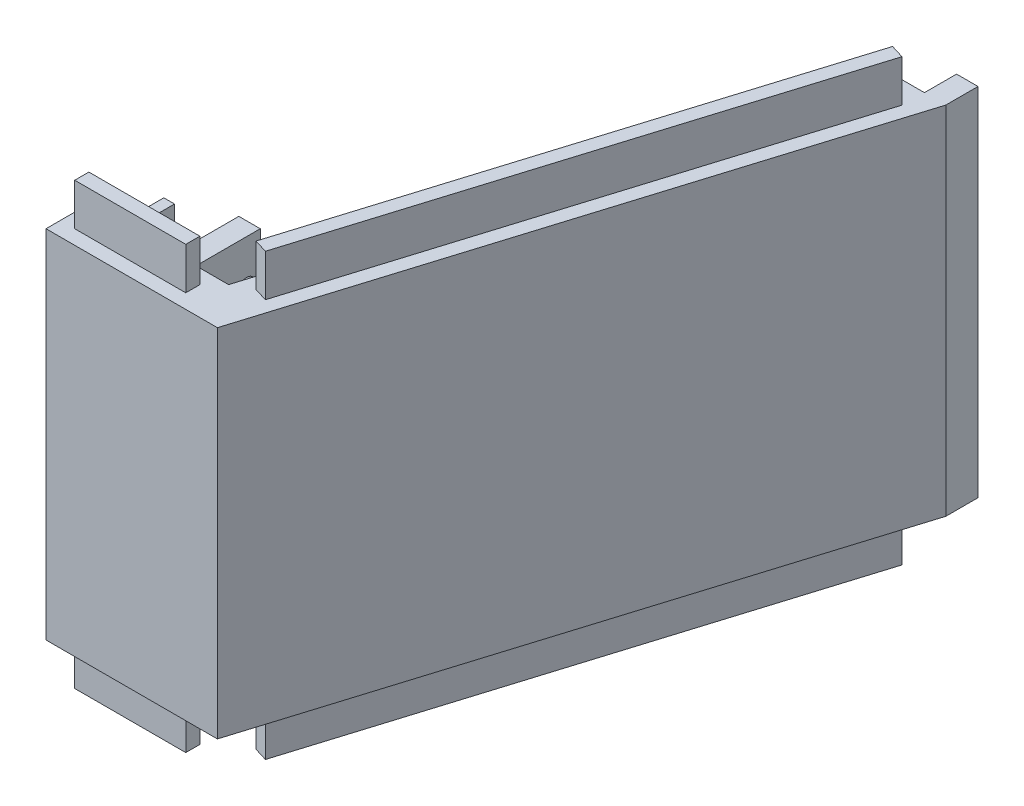
SolidWorks part; units mm, degrees
ref_plane "Front Plane" through (0, 0, 0) normal (1, 0, 0) x (0, 1, 0)
ref_plane "Top Plane" through (0, 0, 0) normal (0, 0, 1) x (0, 1, 0)
ref_plane "Right Plane" through (0, 0, 0) normal (0, 1, 0) x (-1, 0, 0)
sketch "Sketch1" plane through (0, 0, 0) normal (0, 1, 0) x (-1, 0, 0)
  line L0 (-10.3119, 17.5706) -> (29.6881, 147.5706)
  line L1 (-10.3119, 10.0706) -> (-5.3119, 10.0706)
  line L2 (-10.3119, 10.0706) -> (-10.3119, 17.5706)
  line L3 (-10.3119, 17.5706) -> (-5.3119, 17.5706)
  line L4 (-5.3119, 10.0706) -> (-5.3119, 17.5706)
  line L13 (-10.3119, 17.5706) -> (29.6881, 147.5706)
  line L14 (-10.3119, 17.5706) -> (-0.7541, 14.6298)
  line L15 (-10.3119, 17.5706) -> (69.6881, 17.5706) construction
  line L16 (-10.3119, 17.5706) -> (-10.3119, 137.5706) construction
  line L17 (-10.3119, 137.5706) -> (69.6881, 137.5706) construction
  line L18 (69.6881, 17.5706) -> (69.6881, 137.5706) construction
  line L19 (69.6881, 137.5706) -> (29.6881, 137.5706)
  line L20 (69.6881, 137.5706) -> (69.6881, 147.5706)
  line L21 (69.6881, 147.5706) -> (29.6881, 147.5706)
  line L22 (29.6881, 137.5706) -> (29.6881, 147.5706)
  line L23 (29.6881, 147.5706) -> (39.2459, 144.6298)
  line L24 (-0.7541, 14.6298) -> (39.2459, 144.6298)
  line L25 (-5.3119, 17.5706) -> (0.1508, 17.5706)
  dimension "D1" = 7.5
  dimension "D2" = 5
  dimension "D3" = 120
  dimension "D4" = 80
  dimension "D6" = 40
  dimension "D7" = 10
extrude "Boss-Extrude1" add sketch "Sketch1" along normal blind 83.125 contours L24 L19 L20 L21 L23 | L19 L24 L23 L22 | L3 L25 L24 L19 L22 L0 | L14 L2 L1 L4 | L3 L14 L4 region at (7.9071, 0, 13.4507) region at (-13.566, 0, 78.3373) region at (6.9786, 0, 17.0578) region at (-33.743, 0, 142.0805) region at (-53.299, 0, 142.6816)
sketch "Sketch2" plane through (0, 83.125, 0) normal (0, 1, 0) x (-1, 0, 0)
  line L0 (37.0738, 137.5706) -> (0.1508, 17.5706)
  line L1 (37.0738, 137.5706) -> (69.6881, 137.5706)
  line L2 (37.0738, 137.5706) -> (37.0738, 147.5706)
  line L3 (37.0738, 147.5706) -> (69.6881, 147.5706)
  line L4 (69.6881, 137.5706) -> (69.6881, 147.5706)
  line L5 (37.0738, 137.5706) -> (27.5161, 140.5115)
  line L6 (0.1508, 17.5706) -> (-9.407, 20.5115)
  line L7 (27.5161, 140.5115) -> (-9.407, 20.5115)
  line L9 (32.8868, 135.3539) -> (-2.0659, 21.7577)
  line L10 (-2.0659, 21.7577) -> (-5.22, 22.7281)
  line L11 (29.7327, 136.3244) -> (-5.22, 22.7281)
  line L12 (32.8868, 135.3539) -> (29.7327, 136.3244)
  line L13 (40.4238, 140.9206) -> (40.4238, 144.2206)
  line L14 (40.4238, 144.2206) -> (66.3381, 144.2206)
  line L15 (66.3381, 140.9206) -> (66.3381, 144.2206)
  line L16 (40.4238, 140.9206) -> (66.3381, 140.9206)
  line L17 (69.6881, 137.5706) -> (69.6881, 147.5706) construction
  line L18 (29.7327, 136.3244) -> (33.1931, 147.5706)
  line L20 (32.8868, 135.3539) -> (36.6458, 147.5706)
  line L21 (36.6458, 147.5706) -> (33.1931, 147.5706)
  line L22 (40.4238, 144.2206) -> (32.1623, 144.2206)
  line L23 (32.1623, 144.2206) -> (31.1469, 140.9206)
  line L24 (31.1469, 140.9206) -> (40.4238, 140.9206)
  line L25 (-10.3119, 17.5706) -> (29.6881, 147.5706) construction
  dimension "D1" = 3.35
extrude "Boss-Extrude2" add sketch "Sketch2" along normal blind 9.8 contours L9 L12 L11 L10 | L13 L16 L15 L14 region at (-53.381, 83.125, 142.5706) region at (-13.8334, 83.125, 79.041)
ref_plane "Plane1" through (0, 41.5625, 0) normal (0, 1, 0) x (1, 0, 0)
mirror "Mirror1" about plane through (0, 41.5625, 0) normal (0, 1, 0) of "Boss-Extrude2"
sketch "Sketch3" plane through (0, 83.125, 0) normal (0, 1, 0) x (-1, 0, 0)
  line L1 (6.3046, 37.5706) -> (69.6881, 37.5706) construction
  line L2 (6.3046, 37.5706) -> (6.3046, 137.5706) construction
  line L3 (6.3046, 137.5706) -> (69.6881, 137.5706) construction
  line L4 (69.6881, 37.5706) -> (69.6881, 137.5706) construction
  line L5 (69.6881, 37.5706) -> (6.3046, 37.5706)
  line L6 (69.6881, 37.5706) -> (69.6881, 42.5706)
  line L7 (69.6881, 42.5706) -> (6.3046, 42.5706)
  line L8 (6.3046, 37.5706) -> (6.3046, 42.5706)
  line L9 (0.1508, 17.5706) -> (37.0738, 137.5706) construction
  line L10 (57.1881, 37.5706) -> (59.6881, 37.5706)
  line L11 (57.1881, 37.5706) -> (57.1881, 27.5706)
  line L12 (57.1881, 27.5706) -> (59.6881, 27.5706)
  line L13 (59.6881, 37.5706) -> (59.6881, 27.5706)
  line L14 (34.6881, 37.5706) -> (37.1881, 37.5706)
  line L15 (34.6881, 37.5706) -> (34.6881, 27.5706)
  line L16 (34.6881, 27.5706) -> (37.1881, 27.5706)
  line L17 (37.1881, 37.5706) -> (37.1881, 27.5706)
  line L18 (12.1881, 37.5706) -> (14.6881, 37.5706)
  line L19 (12.1881, 37.5706) -> (12.1881, 27.5706)
  line L20 (12.1881, 27.5706) -> (14.6881, 27.5706)
  line L21 (14.6881, 37.5706) -> (14.6881, 27.5706)
  line L22 (57.1881, 27.5706) -> (37.1881, 27.5706)
  line L23 (57.1881, 27.5706) -> (57.1881, 37.5706)
  line L24 (57.1881, 37.5706) -> (37.1881, 37.5706)
  line L25 (37.1881, 27.5706) -> (37.1881, 37.5706)
  line L26 (57.1881, 27.5706) -> (37.1881, 37.5706) construction
  line L27 (57.1881, 37.5706) -> (37.1881, 27.5706) construction
  line L28 (34.6881, 27.5706) -> (14.6881, 27.5706)
  line L29 (34.6881, 27.5706) -> (34.6881, 37.5706)
  line L30 (34.6881, 37.5706) -> (14.6881, 37.5706)
  line L31 (14.6881, 27.5706) -> (14.6881, 37.5706)
  line L32 (34.6881, 27.5706) -> (14.6881, 37.5706) construction
  line L33 (34.6881, 37.5706) -> (14.6881, 27.5706) construction
  line L34 (0.1508, 17.5706) -> (6.3046, 17.5706) construction
  line L35 (0.1508, 17.5706) -> (0.1508, 37.5706) construction
  line L36 (0.1508, 37.5706) -> (6.3046, 37.5706) construction
  line L37 (6.3046, 17.5706) -> (6.3046, 37.5706) construction
  line L38 (0.1508, 17.5706) -> (6.3046, 37.5706) construction
  line L39 (0.1508, 37.5706) -> (6.3046, 17.5706) construction
  point P20 (69.6881, 40.0706)
  point P21 (6.3046, 40.0706)
  point P24 (47.1881, 32.5706)
  point P25 (24.6881, 32.5706)
  point P29 (3.2277, 27.5706)
  line M17 (0.1508, 17.5706) -> (37.0738, 137.5706)
  dimension "D2" = 5
  dimension "D1" = 63.3835
  dimension "D3" = 2.5
  dimension "D4" = 2.5
  dimension "D5" = 2.5
  dimension "D6" = 10
  dimension "D7" = 20
  dimension "D8" = 20
  dimension "D9" = 5.8835
  dimension "D10" = 10
  dimension "D11" = 20
extrude "Boss-Extrude3" [suppressed] add sketch "Sketch3" against normal blind 176 contours L6 L7 L5 M17 | L21 L5 L19 L20 | L17 L5 L15 L16 | L13 L5 L11 L12
sketch "Sketch4" [suppressed] plane through (-14.6881, 0, 0) normal (-1, 0, 0) x (0, -1, 0)
  line L1 (-83.125, 27.5706) -> (-77.625, 27.5706) construction
  line L2 (-83.125, 27.5706) -> (-83.125, 31.6956) construction
  line L3 (-83.125, 31.6956) -> (-77.625, 31.6956) construction
  line L4 (-77.625, 27.5706) -> (-77.625, 31.6956) construction
  circle A0 centre (-77.625, 31.6956) radius 1.9
  circle A1 centre (79.2, 31.6956) radius 1.9
  dimension "D3" = 3.8
  dimension "D1" = 5.5
  dimension "D2" = 4.125
  dimension "D5" = 156.825
extrude "Cut-Extrude2" [suppressed] cut sketch "Sketch4" against normal up to next
sketch "Sketch5" [suppressed] plane through (-37.1881, 0, 0) normal (-1, 0, 0) x (0, -1, 0)
  line L1 (-83.125, 27.5706) -> (-72.625, 27.5706) construction
  line L2 (-83.125, 27.5706) -> (-83.125, 31.6956) construction
  line L3 (-83.125, 31.6956) -> (-72.625, 31.6956) construction
  line L4 (-72.625, 27.5706) -> (-72.625, 31.6956) construction
  circle A0 centre (-72.625, 31.6956) radius 1.9
  circle A3 centre (84.2, 31.6956) radius 1.9
  dimension "D3" = 3.8
  dimension "D5" = 156.825
  dimension "D1" = 4.125
  dimension "D2" = 10.5
extrude "Cut-Extrude3" [suppressed] cut sketch "Sketch5" against normal up to next
sketch "Sketch6" [suppressed] plane through (-59.6881, 0, 0) normal (-1, 0, 0) x (0, -1, 0)
  line L0 (-83.125, 17.5706) -> (-83.125, 37.5706) construction
  line L1 (-83.125, 27.5706) -> (-67.625, 27.5706) construction
  line L2 (-83.125, 27.5706) -> (-83.125, 31.4206) construction
  line L3 (-83.125, 31.4206) -> (-67.625, 31.4206) construction
  line L4 (-67.625, 27.5706) -> (-67.625, 31.4206) construction
  circle A0 centre (-67.625, 31.4206) radius 1.9
  circle A1 centre (44.965, 31.4206) radius 1.9
  dimension "D3" = 3.8
  dimension "D1" = 3.85
  dimension "D2" = 15.5
extrude "Cut-Extrude4" [suppressed] cut sketch "Sketch6" against normal up to next
sketch "Sketch7" plane through (0, 83.125, 0) normal (0, 1, 0) x (-1, 0, 0)
  line L1 (37.0738, 137.5706) -> (69.6881, 137.5706) construction
  line L2 (37.0738, 137.5706) -> (37.0738, 127.5706) construction
  line L3 (37.0738, 127.5706) -> (69.6881, 127.5706) construction
  line L4 (69.6881, 137.5706) -> (69.6881, 127.5706) construction
  line L5 (69.6881, 137.5706) -> (62.1881, 137.5706) construction
  line L6 (69.6881, 137.5706) -> (69.6881, 127.5706) construction
  line L7 (69.6881, 127.5706) -> (62.1881, 127.5706) construction
  line L8 (62.1881, 137.5706) -> (62.1881, 127.5706) construction
  line L9 (62.1881, 137.5706) -> (59.6881, 137.5706)
  line L10 (62.1881, 137.5706) -> (62.1881, 127.5706)
  line L11 (62.1881, 127.5706) -> (59.6881, 127.5706)
  line L12 (59.6881, 137.5706) -> (59.6881, 127.5706)
  line L13 (59.6881, 137.5706) -> (49.6881, 137.5706) construction
  line L14 (59.6881, 137.5706) -> (59.6881, 127.5706) construction
  line L15 (59.6881, 127.5706) -> (49.6881, 127.5706) construction
  line L16 (49.6881, 137.5706) -> (49.6881, 127.5706) construction
  line L17 (49.6881, 137.5706) -> (44.6881, 137.5706)
  line L18 (49.6881, 137.5706) -> (49.6881, 127.5706)
  line L19 (49.6881, 127.5706) -> (44.6881, 127.5706)
  line L20 (44.6881, 137.5706) -> (44.6881, 127.5706)
  line L21 (44.6881, 137.5706) -> (37.0738, 137.5706) construction
  line L22 (44.6881, 137.5706) -> (44.6881, 127.5706) construction
  line L23 (44.6881, 127.5706) -> (37.0738, 127.5706) construction
  line L24 (37.0738, 137.5706) -> (37.0738, 127.5706) construction
  line L25 (44.6881, 127.5706) -> (49.6881, 127.5706)
  line L26 (44.6881, 127.5706) -> (44.6881, 122.5706)
  line L27 (44.6881, 122.5706) -> (49.6881, 122.5706)
  line L28 (49.6881, 127.5706) -> (49.6881, 122.5706)
  line M10 (37.0738, 137.5706) -> (69.6881, 137.5706)
  dimension "D3" = 2.5
  dimension "D2" = 7.5
  dimension "D4" = 5
  dimension "D6" = 7.6143
  dimension "D7" = 5
extrude "Boss-Extrude4" add sketch "Sketch7" against normal up to surface (83.125 mm away) contours L20 L19 L18 M10 | L28 L19 L26 L27 | L12 L11 L10 M10 region at (-60.9381, 83.125, 132.5706) region at (-47.1881, 83.125, 132.5706) region at (-47.1881, 83.125, 125.0706) up to face at (-53.381, 0, 142.5706)
sketch "Sketch8" plane through (-49.6881, 0, 0) normal (-1, 0, 0) x (0, -1, 0)
  line L0 (0, 135.3539) -> (0, 21.7577) construction
  line L1 (-83.125, 122.5706) -> (-72.9725, 122.5706) construction
  line L2 (-83.125, 122.5706) -> (-83.125, 125.7206) construction
  line L3 (-83.125, 125.7206) -> (-72.9725, 125.7206) construction
  line L4 (-72.9725, 122.5706) -> (-72.9725, 125.7206) construction
  circle A0 centre (-72.9725, 125.7206) radius 1.9
  circle A1 centre (-10.1525, 125.7206) radius 1.9
  dimension "D3" = 3.8
  dimension "D1" = 3.15
  dimension "D2" = 10.1525
  dimension "D5" = 10.1525
extrude "Cut-Extrude5" cut sketch "Sketch8" against normal up to next
sketch "Sketch9" plane through (-62.1881, 0, 0) normal (-1, 0, 0) x (0, -1, 0)
  line L2 (-83.125, 127.5706) -> (-72.9725, 127.5706) construction
  line L3 (-83.125, 127.5706) -> (-83.125, 130.8206) construction
  line L4 (-83.125, 130.8206) -> (-72.9725, 130.8206) construction
  line L5 (-72.9725, 127.5706) -> (-72.9725, 130.8206) construction
  circle A1 centre (-72.9725, 130.8206) radius 1.9
  circle A2 centre (-18.9025, 130.8206) radius 1.9
  circle A3 centre (-10.1525, 130.8206) radius 1.9
  circle A4 centre (-72.9725, 125.7206) radius 1.9 construction
  circle A5 centre (-10.1525, 125.7206) radius 1.9 construction
  circle A6 centre (-64.2225, 130.8206) radius 1.9
  dimension "D3" = 3.8
  dimension "D2" = 10.1525
  dimension "D1" = 3.25
  dimension "D6" = 62.82
  dimension "D8" = 54.07
  dimension "D9" = 54.07
extrude "Cut-Extrude6" cut sketch "Sketch9" against normal up to next
sketch "Sketch10" plane through (-62.1881, 0, 0) normal (-1, 0, 0) x (0, -1, 0)
  line L0 (-83.125, 137.5706) -> (0, 137.5706) construction
  line L1 (-83.125, 122.5706) -> (-58.125, 122.5706) construction
  line L2 (-83.125, 122.5706) -> (-83.125, 137.5706) construction
  line L3 (-83.125, 137.5706) -> (-58.125, 137.5706) construction
  line L4 (-58.125, 122.5706) -> (-58.125, 137.5706) construction
  line L5 (0, 122.5706) -> (-83.125, 122.5706) construction
  line L6 (-58.125, 137.5706) -> (-25, 137.5706)
  line L7 (-58.125, 137.5706) -> (-58.125, 122.5706)
  line L8 (-58.125, 122.5706) -> (-25, 122.5706)
  line L9 (-25, 137.5706) -> (-25, 122.5706)
  line L11 (-25, 122.5706) -> (0, 122.5706) construction
  line L12 (-25, 122.5706) -> (-25, 137.5706) construction
  line L13 (-25, 137.5706) -> (0, 137.5706) construction
  line L14 (0, 122.5706) -> (0, 137.5706) construction
  dimension "D1" = 25
  dimension "D2" = 25
extrude "Cut-Extrude7" cut sketch "Sketch10" against normal up to surface (17.5 mm away) up to face at (-44.6881, 72.9725, 123.8206)
equation "\"whitekey_cutout_length\"= 101.5"
equation "\"key_mount_recess_length\"=50"
equation "\"key_mount_recess_height\"=12.5"
equation "\"key_mount_recess_depth\"=1.5"
equation "\"wall_thickness\"=10"
equation "\"guide_brace_height\"=20"
equation "\"guide_brace_thickness\"=2"
equation "\"dowel_recess_depth\"=10"
equation "\"dowel_recess_offset\"=3.25"
equation "\"dowel_insert_tolerance\"=0.1"
equation "\"base_mount_height\"=40"
equation "\"base_rear_length\"=80"
equation "\"base_front_length\"=111.5"
equation "\"screw_hole_wall_offset\"=7.25"
equation "\"screw_hole_edge_inset\"=\"dowel_recess_depth\"/2"
equation "\"screw_hole_diameter\"=3.8"
equation "\"screw_head_hole_diameter\"=6.7"
equation "\"screw_nut_hole_side_len\"=3.5"
equation "\"screw_nut_recess_offset\"=0.35"
equation "\"screw_head_and_nut_recess_depth\"=2.5"
equation "\"screw_shaft_diameter\"=3.5"
equation "\"switch_board_width\"=30"
equation "\"switch_board_thickness\"=1.6"
equation "\"switch_board_wall_offset\"=11.5"
equation "\"heatset_insert_hole_diameter\"=4.8"
equation "\"heatset_insert_hole_depth\"=3.8"
equation "\"front_rear_panel_width\"=23.75"
equation "\"front_panel_height\"=24"
equation "\"front_rear_panel_recess_depth\"=5"
equation "\"rod_diameter\"=5"
equation "\"rod_head_diameter\"=8"
equation "\"rod_length_adj\"=0.5"
equation "\"rod_insert_length\"=2.8"
equation "\"switch_black_key_mount_height\"=8"
equation "\"switch_white_key_mount_height\"=3"
equation "\"D7@Sketch1\"=\"wall_thickness\""
equation "\"D5@Sketch1\"=\"wall_thickness\""
equation "\"D2@Sketch1\"=\"wall_thickness\"/2"
equation "\"D4@Sketch1\"=\"base_rear_length\""
equation "\"D3@Sketch1\"=\"base_mount_height\"*3"
equation "\"D1@Sketch1\"=\"wall_thickness\"*0.75"
equation "\"D1@Boss-Extrude1\"=\"front_rear_panel_width\"*3.5"
equation "\"D1@Sketch2\"=\"dowel_recess_offset\"+\"dowel_insert_tolerance\""
equation "\"D1@Boss-Extrude2\"=\"dowel_recess_depth\"-\"dowel_insert_tolerance\"*2"
equation "\"D2@Sketch3\"=\"wall_thickness\"/2"
equation "\"D3@Sketch3\"=\"wall_thickness\"/4"
equation "\"D4@Sketch3\"=\"wall_thickness\"/4"
equation "\"D5@Sketch3\"=\"wall_thickness\"/4"
equation "\"D6@Sketch3\"=\"wall_thickness\""
equation "\"D7@Sketch3\"=\"wall_thickness\"*2"
equation "\"D8@Sketch3\"=\"wall_thickness\"*2"
equation "\"D10@Sketch3\"=\"wall_thickness\""
equation "\"D3@Sketch4\"=\"screw_hole_diameter\""
equation "\"D3@Sketch5\"=\"screw_hole_diameter\""
equation "\"D3@Sketch6\"=\"screw_hole_diameter\""
equation "\"D1@Sketch7\"=\"wall_thickness\""
equation "\"D2@Sketch7\"=\"wall_thickness\"*0.75"
equation "\"D3@Sketch7\"=\"wall_thickness\"/4"
equation "\"D4@Sketch7\"=\"wall_thickness\"/2"
equation "\"D5@Sketch7\"=\"wall_thickness\""
equation "\"D7@Sketch7\"=\"wall_thickness\"/2"
equation "\"D3@Sketch8\"=\"screw_hole_diameter\""
equation "\"D3@Sketch9\"=\"screw_hole_diameter\""
